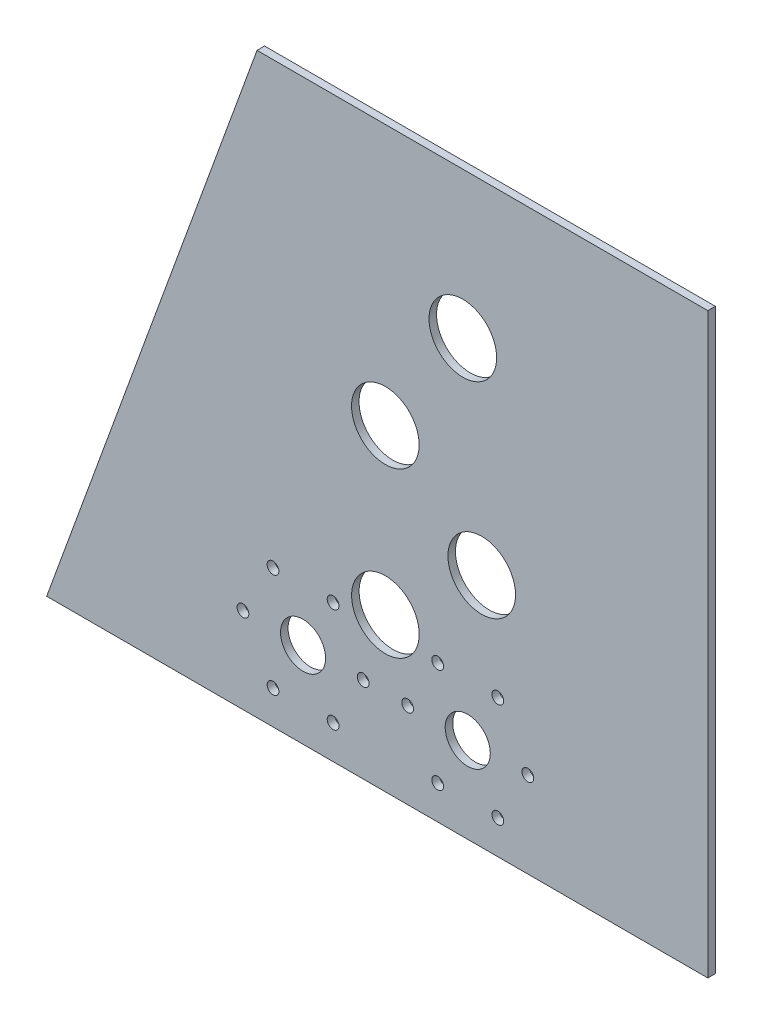
SolidWorks part; units mm, degrees
ref_plane "Front Plane" through (0, 0, 0) normal (0, 0, 1) x (1, 0, 0)
ref_plane "Top Plane" through (0, 0, 0) normal (0, 1, 0) x (1, 0, 0)
ref_plane "Right Plane" through (0, 0, 0) normal (1, 0, 0) x (0, 0, -1)
sketch "Sketch1" plane through (0, 0, 0) normal (0, 0, 1) x (1, 0, 0)
  line B0 (-190.3736, 244.2507) -> (0.1264, 244.2507)
  line B1 (0.1264, 244.2507) -> (0.1264, 0)
  line B2 (0.1264, 0) -> (-279.2736, 0)
  line B3 (-279.2736, 0) -> (-190.3736, 244.2507)
  line B4 (-101.3292, 36.2409) -> (-75.9292, 36.2409) construction
  line B5 (-170.9252, 36.2409) -> (-145.5252, 36.2409) construction
  circle B6 centre (-103.4058, 182.3706) radius 14.2875
  circle B7 centre (-136.1547, 134.0708) radius 14.2875
  circle B8 centre (-95.4216, 99.6001) radius 14.2875
  circle B9 centre (-136.1272, 64.8068) radius 14.2875
  circle B10 centre (-101.3292, 36.2409) radius 9.525
  circle B11 centre (-170.9252, 36.2409) radius 9.525
  circle B12 centre (-101.3292, 36.2409) radius 25.4 construction
  circle B13 centre (-101.3292, 36.2409) radius 25.4 construction
  circle B14 centre (-101.3292, 36.2409) radius 25.4 construction
  circle B15 centre (-101.3292, 36.2409) radius 25.4 construction
  circle B16 centre (-101.3292, 36.2409) radius 25.4 construction
  circle B17 centre (-101.3292, 36.2409) radius 25.4 construction
  circle B18 centre (-126.7292, 36.2409) radius 2.4892
  circle B19 centre (-114.0292, 58.238) radius 2.4892
  circle B20 centre (-88.6292, 58.238) radius 2.4892
  circle B21 centre (-170.9252, 36.2409) radius 25.4 construction
  circle B22 centre (-158.2252, 58.238) radius 2.4892
  circle B23 centre (-145.5252, 36.2409) radius 2.4892
  circle B24 centre (-114.0292, 14.2439) radius 2.4892
  circle B25 centre (-88.6292, 14.2439) radius 2.4892
  circle B26 centre (-75.9292, 36.2409) radius 2.4892
  circle B27 centre (-145.5252, 36.2409) radius 2.4892
  circle B28 centre (-88.6292, 14.2439) radius 2.4892
  circle B29 centre (-114.0292, 14.2439) radius 2.4892
  circle B30 centre (-126.7292, 36.2409) radius 2.4892
  circle B31 centre (-114.0292, 58.238) radius 2.4892
  circle B32 centre (-88.6292, 58.238) radius 2.4892
  circle B33 centre (-158.2252, 14.2439) radius 2.4892
  circle B34 centre (-183.6252, 14.2439) radius 2.4892
  circle B35 centre (-196.3252, 36.2409) radius 2.4892
  circle B36 centre (-183.6252, 58.238) radius 2.4892
  circle B37 centre (-158.2252, 58.238) radius 2.4892
sketch_block_instance "Block-Gearbox_Plate1-1"
sketch_block "Block-Gearbox_Plate1" parameters "D3"=28.575, "D4"=28.575, "D5"=28.575, "D6"=28.575, "D7"=19.05, "D8"=19.05, "D9"=50.8, "D10"=50.8, "D11"=4.9784, "D12"=4.9784, "D1"=190.5, "D2"=279.4, "D13"=25.4, "D14"=25.4
extrude "Boss-Extrude1" add sketch "Sketch1" along normal blind 3.175 contours B3 B2 B1 B0 B36 B35 B34 B33 B26 B25 B24 B23 B22 B20 B19 B18 B11 B10 B9 B8 B7 B6 region at (-118.5378, 115.312, 0)
